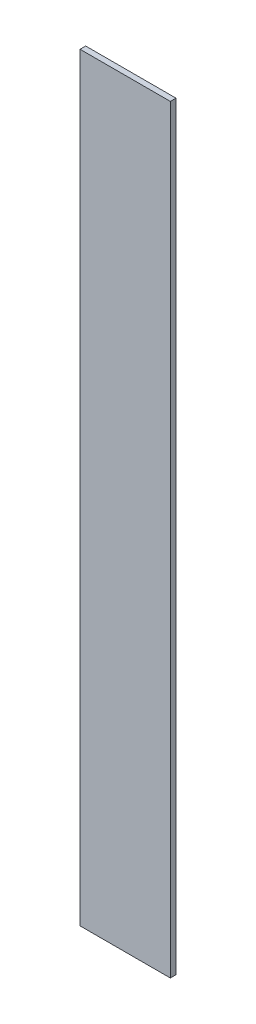
SolidWorks part; units mm, degrees
material "Acrylic (Medium-high impact)"
ref_plane "Front Plane" through (0, 0, 0) normal (0, 0, 1) x (1, 0, 0)
ref_plane "Top Plane" through (0, 0, 0) normal (0, 1, 0) x (1, 0, 0)
ref_plane "Right Plane" through (0, 0, 0) normal (1, 0, 0) x (0, 0, -1)
sketch "Sketch1" plane through (0, 0, 0) normal (0, 1, 0) x (1, 0, 0)
  line L0 (0, 0) -> (0, 76.2) construction
  line L2 (25.4, 68.667) -> (-25.4, 68.667)
  line L3 (25.4, 68.667) -> (25.4, 71.842)
  line L4 (25.4, 71.842) -> (-25.4, 71.842)
  line L5 (-25.4, 68.667) -> (-25.4, 71.842)
  line L6 (25.4, 68.667) -> (-25.4, 71.842) construction
  line L7 (25.4, 71.842) -> (-25.4, 68.667) construction
  circle A0 centre (0, 0) radius 76.2 construction
  point P4 (0, 70.2545)
  dimension "D1" = 152.4
  dimension "D2" = 3.175
  dimension "D3" = 50.8
extrude "Boss-Extrude1" add sketch "Sketch1" along normal blind 427.1518
